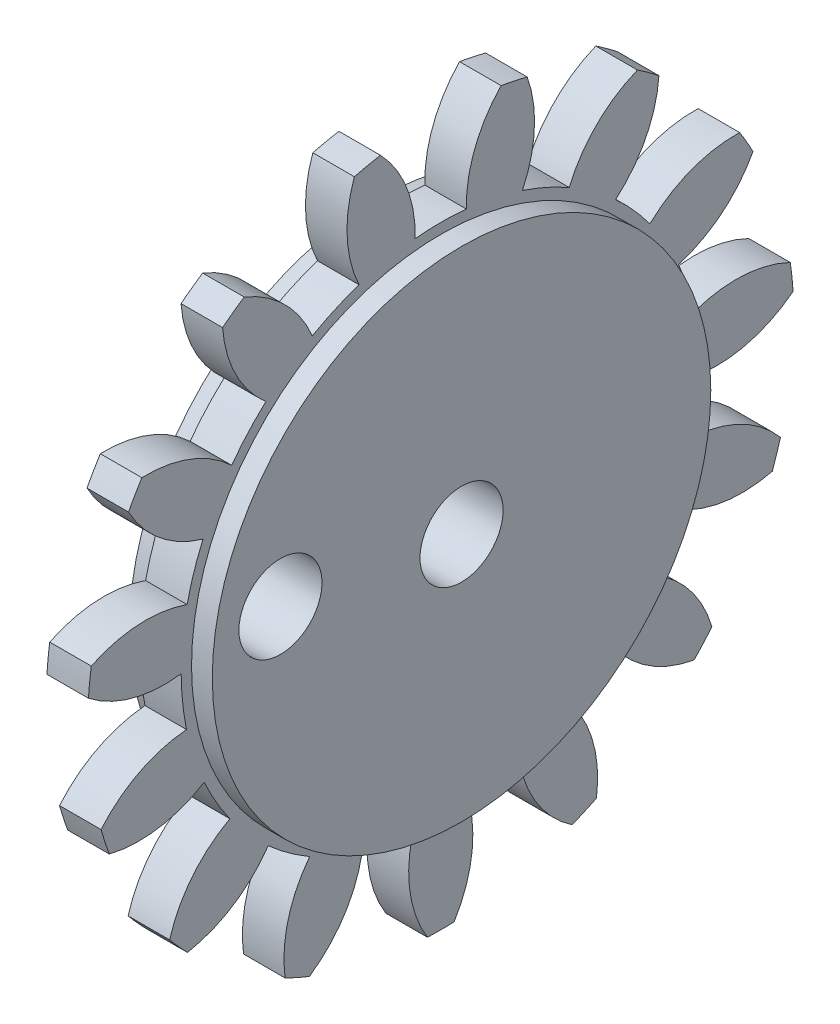
SolidWorks part; units mm, degrees
ref_plane "Plane1" through (0, 0, 0) normal (0, 0, 1) x (1, 0, 0)
ref_plane "Plane2" through (0, 0, 0) normal (0, 1, 0) x (1, 0, 0)
ref_plane "Plane3" through (0, 0, 0) normal (1, 0, 0) x (0, 0, -1)
other "Configuration Table"
sketch "HoldingSke" plane through (0, 0, 0) normal (0, 1, 0) x (1, 0, 0)
  line L0 (0, 0) -> (98.1381, -26.296)
  line L1 (-15, 0) -> (100, 0) construction
  line L2 (0, 0) -> (-2.1039, 2.3779)
  line L3 (0, 0) -> (-11.863, 4.5341)
  line L4 (0, 0) -> (8.3417, 2.2352)
  line L5 (0, 0) -> (-11.8993, -4.4381)
  line L6 (0, 0) -> (-5.2639, -3.5516)
  line L7 (-2.1039, 2.3779) -> (0.6298, 14.7802)
  line L8 (-76.2, 54.61) -> (-61.976, 54.61)
  line L9 (-67.7845, 28.3722) -> (-49.3413, 33.142)
  line L10 (-76.2, 71.12) -> (104.1128, 71.12)
  line L11 (0, 0) -> (-6.35, 0)
  line L12 (-76.2, 101.6) -> (-75.9714, 101.6)
  line L13 (24.9733, 27.94) -> (52.9518, 28.4284)
  line L14 (24.9733, 27.94) -> (24.9746, 27.94)
  line L15 (24.9733, 27.94) -> (100.4006, 29.5858)
  circle A0 centre (0, 0) radius 6.35
  circle A1 centre (0, 0) radius 38.1
  circle A2 centre (0, 0) radius 38.1
  circle A3 centre (0, 0) radius 6.35
  dimension "Num_teeth" = 15
  dimension "H" = 19.05
  dimension "Pitch_radius" = 180.3128
  dimension "Width" = 6.35
  dimension "Thickness" = 6.35
sketch "BasProSke" plane through (0, 0, 0) normal (0, 1, 0) x (1, 0, 0)
  line L0 (-10, 0) -> (60, 0) construction
  line L1 (0, 0) -> (0, 53.975)
  line L2 (0, 0) -> (6.35, 0)
  line L3 (6.35, 0) -> (6.35, 53.975)
  line L4 (6.35, 53.975) -> (0, 53.975)
  dimension "Thickness" = 6.35
  dimension "Diameter" = 107.95
revolve "Base-Revolve" add sketch "BasProSke" angle 360 about L0
sketch "TooCutSke" plane through (0, 0, 0) normal (1, 0, 0) x (0, 0, -1)
  line L1 (0, 0) -> (0, 107) construction
  line L2 (0, 0) -> (-5.3779, 47.3204) construction
  line L3 (0, 0) -> (-19.7119, 92.7371) construction
  line L4 (-5.3779, 47.3204) -> (-9.8559, 46.3685) construction
  arc A0 (3.9155, 39.4926) -> (-3.9155, 39.4926) centre (0, 0) ccw
  arc A1 (9.2414, 53.2038) -> (-9.2414, 53.2038) centre (0, 0) ccw
  circle A2 centre (0, 0) radius 47.625 construction
  circle A3 centre (0, 0) radius 46.108 construction
  arc A4 (-3.9155, 39.4926) -> (-9.2414, 53.2038) centre (-22.9591, 39.9854) ccw
  arc A5 (9.2414, 53.2038) -> (3.9155, 39.4926) centre (22.9591, 39.9854) ccw
extrude "ToothCut" cut sketch "TooCutSke" along normal through all
fillet "Breaks" [suppressed] radius 0.127 tangent propagation no
fillet "RootFillets" [suppressed] radius 1.5888
pattern_circular "TeethCuts" count 15 every 24 about axis through (-10, 0, 0) along (1, 0, 0) of "ToothCut", "RootFillets", "Breaks"
sketch "HubNeaOneSke" plane through (0, 0, 0) normal (-1, 0, 0) x (0, 0, 1)
  circle A0 centre (0, 0) radius 38.1
  dimension "Diameter" = 76.2
extrude "HubNearOne" [suppressed] add sketch "HubNeaOneSke" along normal blind 6.3501
sketch "HubNeaBotSke" plane through (0, 0, 0) normal (-1, 0, 0) x (0, 0, 1)
  circle A0 centre (0, 0) radius 38.1
  dimension "Diameter" = 76.2
extrude "HubNearBoth" add sketch "HubNeaBotSke" along normal blind 3.175
ref_plane "FarPln" through (6.35, 0, 0) normal (1, 0, 0) x (0, 0, -1)
sketch "HubFarSke" plane through (6.35, 0, 0) normal (1, 0, 0) x (0, 0, -1)
  circle A0 centre (0, 0) radius 38.1
  dimension "Diameter" = 76.2
extrude "HubFar" add sketch "HubFarSke" along normal blind 3.175
sketch "BorSke" plane through (0, 0, 0) normal (1, 0, 0) x (0, 0, -1)
  circle A0 centre (0, 0) radius 6.35
  dimension "Diameter" = 12.7
extrude "Bore" cut sketch "BorSke" along normal mid plane 25.4001
sketch "KeySke" plane through (0, 0, 0) normal (1, 0, 0) x (0, 0, -1)
  line L0 (-1.5875, 0) -> (-1.5875, 7.874)
  line L1 (-1.5875, 7.874) -> (1.5875, 7.874)
  line L2 (1.5875, 7.874) -> (1.5875, 0)
  line L3 (0, 0) -> (0, 34) construction
  line L4 (-1.5875, 0) -> (1.5875, 0)
  dimension "Width" = 3.175
extrude "Keyway" [suppressed] cut sketch "KeySke" along normal mid plane 25.4001
pattern_circular "Keyway2" [suppressed] count 2 every 90 about axis through (-10, 0, 0) along (1, 0, 0) reverse direction yes
sketch "Sketch1" plane through (-3.175, 0, 0) normal (-1, 0, 0) x (0, 0, 1)
  line L0 (0, 0) -> (27.6826, 4.2691) construction
  line L1 (0, 0) -> (46.7437, 26.9875) construction
  circle A0 centre (27.6826, 4.2691) radius 6.35
  arc A1 (47.7296, 25.2029) -> (45.6911, 28.7336) centre (0, 0) ccw construction
  circle A2 centre (0, 0) radius 28.0098 construction
  circle A3 centre (24.2572, 14.0049) radius 6.35 construction
  dimension "D1" = 12.7
extrude "Cut-Extrude1" cut sketch "Sketch1" against normal through all
scale "Scale1" bodies to scale 108 scale about centroid uniform scaling yes scale factor 0.75
equation "' \"Pitch@HoldingSke\" = 4"
equation "' \"Num_teeth@HoldingSke\" = 12"
equation "' \"Ap@HoldingSke\" =  20"
equation "' \"Ap@HoldingSke\" = 20"
equation "' \"Width@HoldingSke\" = 0.5"
equation "' \"Hub_dia@HoldingSke\"= 1"
equation "' \"Hub_dia@HoldingSke\" = 1"
equation "' \"Overall_len@HoldingSke\" = 1.0"
equation "' \"Bore@HoldingSke\" = 0.75"
equation "' \"T_dim@HoldingSke\" = 0.85"
equation "' \"Width@KeySke\" = 0.25"
equation "' \"Show_teeth@HoldingSke\" = 13"
equation "' \"Backlash@HoldingSke\" = 0.009"
equation "' \"Addendum_fac@HoldingSke\" = 1.0"
equation "' \"Dedendum_fac@HoldingSke\" = 1.25"
equation "' \"Dedendum_add@HoldingSke\" = 0.00005"
equation "' \"Clearance_fac@HoldingSke\" = 0.25"
equation "' \"Pitch@HoldingSke\" = 0.5"
equation "' \"Num_teeth@HoldingSke\" = 23"
equation "' \"Show_teeth@HoldingSke\" = 23"
equation "' \"Backlash@HoldingSke\" = 0.0375"
equation "\"Overcut_dia@TooCutSke\" = (\"Num_teeth@HoldingSke\" + 2 * \"Addendum_fac@HoldingSke\") / \"Pitch@HoldingSke\" + 0.002"
equation "\"Pitch_dia@TooCutSke\" = \"Num_teeth@HoldingSke\" / \"Pitch@HoldingSke\""
equation "\"Base_dia@TooCutSke\" = \"Num_teeth@HoldingSke\" / \"Pitch@HoldingSke\" * cos((\"Ap@HoldingSke\"  * 3.14159265 / 180))"
equation "\"Root_dia@TooCutSke\" = (\"Num_teeth@HoldingSke\" + 2) / \"Pitch@HoldingSke\" - 2 * (\"Addendum_fac@HoldingSke\" + \"Dedendum_fac@HoldingSke\") / \"Pitch@HoldingSke\" - \"Dedendum_add@HoldingSke\" * 2"
equation "\"Half_ang@TooCutSke\" = 180 / \"Num_teeth@HoldingSke\""
equation "\"Half_CT@TooCutSke\" = \"Num_teeth@HoldingSke\" / \"Pitch@HoldingSke\" * sin((3.14159265 / 2 / \"Num_teeth@HoldingSke\")) / 2 - 7 * \"Backlash@HoldingSke\" / 4"
equation "\"Flank_rad@TooCutSke\" = \"Num_teeth@HoldingSke\" / \"Pitch@HoldingSke\" / 5"
equation "\"Radius@RootFillets\" = \"Clearance_fac@HoldingSke\" / \"Pitch@HoldingSke\" + \"Dedendum_add@HoldingSke\""
equation "\"Break_rad@Breaks\" = 0.02 / \"Pitch@HoldingSke\""
equation "\"Thickness@HoldingSke\" = \"Width@HoldingSke\""
equation "\"OAL@HoldingSke\" = \"Thickness@HoldingSke\""
equation "\"MHD@HoldingSke\" = (\"Num_teeth@HoldingSke\" + 2) / \"Pitch@HoldingSke\" - 2 * (\"Addendum_fac@HoldingSke\" + \"Dedendum_fac@HoldingSke\")  / \"Pitch@HoldingSke\" - \"Dedendum_add@HoldingSke\" * 2"
equation "\"MBD@HoldingSke\" = (\"Num_teeth@HoldingSke\" + 2) / \"Pitch@HoldingSke\" - 2 * (\"Addendum_fac@HoldingSke\" + \"Dedendum_fac@HoldingSke\")  / \"Pitch@HoldingSke\" - \"Dedendum_add@HoldingSke\" * 2 - 0.002"
equation "\"MHD@HoldingSke\" = ((sgn( \"MHD@HoldingSke\" - \"Hub_dia@HoldingSke\" )-1)*( \"MHD@HoldingSke\" - \"Hub_dia@HoldingSke\" ))/-2+ \"Hub_dia@HoldingSke\""
equation "\"MBD@HoldingSke\" = ((sgn( \"MBD@HoldingSke\" - \"Bore@HoldingSke\" )-1)*( \"MBD@HoldingSke\" - \"Bore@HoldingSke\" ))/-2+ \"Bore@HoldingSke\""
equation "\"OAL@HoldingSke\" = ((sgn( \"OAL@HoldingSke\" - \"Overall_len@HoldingSke\" )+1)*( \"OAL@HoldingSke\" - \"Overall_len@HoldingSke\" ))/2 + \"Overall_len@HoldingSke\" + 0.000002"
equation "\"Num_teeth@TeethCuts\" = int( \"Show_teeth@HoldingSke\" ) + 1"
equation "\"Num_teeth@TeethCuts\" = ((sgn( \"Num_teeth@TeethCuts\" - \"Num_teeth@HoldingSke\" )-1)*( \"Num_teeth@TeethCuts\" - \"Num_teeth@HoldingSke\" ))/-2+ \"Num_teeth@HoldingSke\""
equation "\"Num_teeth@TeethCuts\" = ((sgn( \"Num_teeth@TeethCuts\" - 2.0)+1)*( \"Num_teeth@TeethCuts\" - 2.0))/2 +2.0"
equation "\"Angle@TeethCuts\" = 360.0 / \"Num_teeth@HoldingSke\""
equation "\"Diameter@BasProSke\" = (\"Num_teeth@HoldingSke\" + 2 * \"Addendum_fac@HoldingSke\") / \"Pitch@HoldingSke\""
equation "\"Thickness@BasProSke\"  = \"Thickness@HoldingSke\""
equation "' \"Fillet_rad@BasProSke\" =  \"Thickness@HoldingSke\" * 0.05"
equation "' \"Fillet_rad@BasProSke\" = \"Thickness@HoldingSke\" * 0.05"
equation "\"MHD@HoldingSke\" = ((sgn( \"MHD@HoldingSke\" - \"Root_dia@TooCutSke\" )-1)*( \"MHD@HoldingSke\" - \"Root_dia@TooCutSke\" ))/-2+ \"Root_dia@TooCutSke\""
equation "\"Diameter@HubNeaOneSke\" = \"MHD@HoldingSke\""
equation "\"Length@HubNearOne\" = \"OAL@HoldingSke\" - \"Thickness@BasProSke\""
equation "\"Diameter@HubNeaBotSke\" = \"MHD@HoldingSke\""
equation "\"Length@HubNearBoth\" = ( \"OAL@HoldingSke\" - \"Thickness@BasProSke\" ) / 2.0"
equation "\"Thickness@FarPln\" = \"Thickness@BasProSke\""
equation "\"Diameter@HubFarSke\" = \"MHD@HoldingSke\""
equation "\"Length@HubFar\" = ( \"OAL@HoldingSke\" - \"Thickness@BasProSke\" ) / 2.0"
equation "\"Diameter@BorSke\" = \"MBD@HoldingSke\""
equation "\"D1@Bore\" = \"OAL@HoldingSke\" * 2.0"
equation "\"D1@Keyway\" = \"OAL@HoldingSke\" * 2.0"
equation "\"Offset@KeySke\" = \"T_dim@HoldingSke\" - \"MBD@HoldingSke\" / 2.0"
